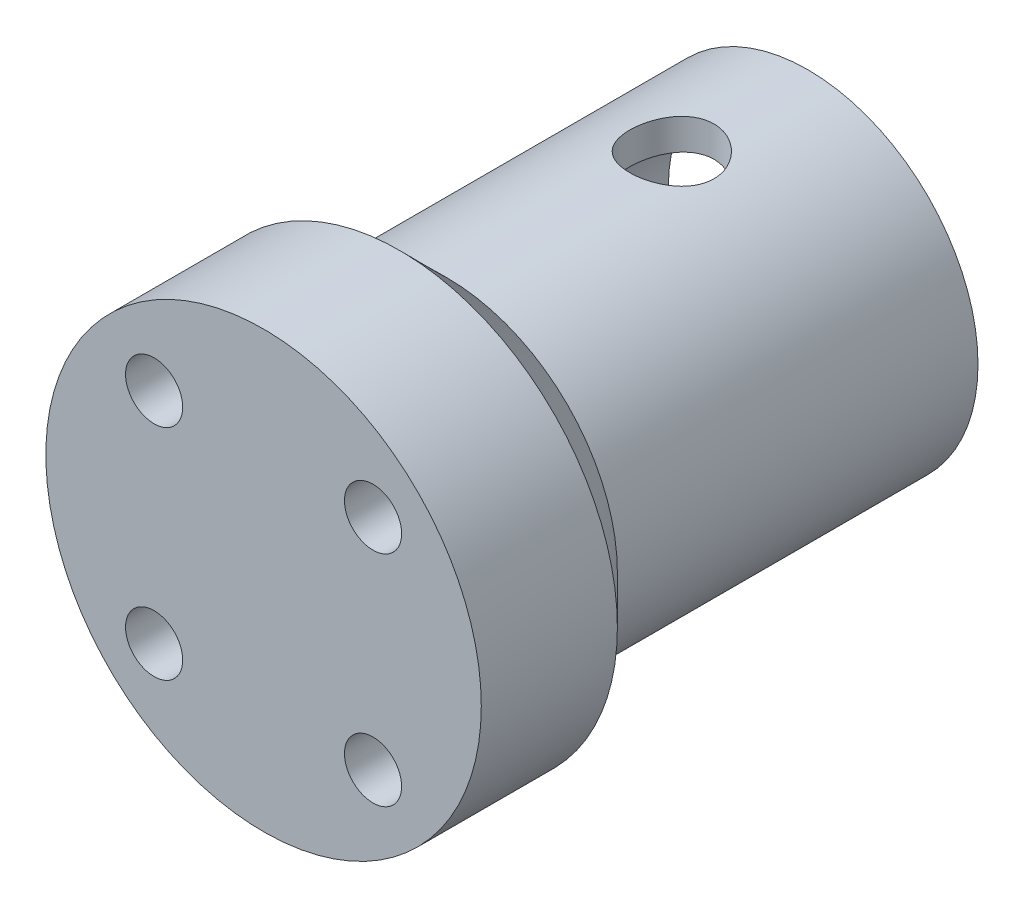
SolidWorks part; units mm, degrees
material "ABS"
ref_plane "前视基准面" through (0, 0, 0) normal (0, 0, 1) x (1, 0, 0)
ref_plane "上视基准面" through (0, 0, 0) normal (0, 1, 0) x (1, 0, 0)
ref_plane "右视基准面" through (0, 0, 0) normal (1, 0, 0) x (0, 0, -1)
sketch "草图1" plane through (0, 0, 0) normal (0, 0, 1) x (1, 0, 0)
  circle A0 centre (0, 0) radius 16
extrude "凸台-拉伸1" add sketch "草图1" along normal blind 10
sketch "草图2" plane through (0, 0, 0) normal (0, 0, -1) x (-1, 0, 0)
  circle A0 centre (0, 0) radius 10.25
  circle A1 centre (0, 0) radius 12.5
extrude "凸台-拉伸2" add sketch "草图2" along normal blind 30
sketch "草图3" plane through (0, 0, 10) normal (0, 0, 1) x (1, 0, 0)
  line L1 (-8.0442, 8.0442) -> (8.0442, 8.0442) construction
  line L2 (-8.0442, 8.0442) -> (-8.0442, -8.0442) construction
  line L3 (-8.0442, -8.0442) -> (8.0442, -8.0442) construction
  line L4 (8.0442, 8.0442) -> (8.0442, -8.0442) construction
  line L5 (-8.0442, 8.0442) -> (8.0442, -8.0442) construction
  line L6 (-8.0442, -8.0442) -> (8.0442, 8.0442) construction
  circle A0 centre (-8.0442, 8.0442) radius 2.1
  circle A1 centre (8.0442, 8.0442) radius 2.1
  circle A2 centre (8.0442, -8.0442) radius 2.1
  circle A3 centre (-8.0442, -8.0442) radius 2.1
  point P0 (0, 0)
extrude "切除-拉伸1" cut sketch "草图3" against normal blind 8
sketch "草图5" plane through (0, 0, 0) normal (0, 1, 0) x (1, 0, 0)
  line L0 (0, 0) -> (0, 20) construction
  circle A0 centre (0, 20) radius 3.1
extrude "切除-拉伸2" cut sketch "草图5" against normal mid plane 30
chamfer "倒角1" distance 3.5 angle 45 1 edges at (12.5, 0, 0)
